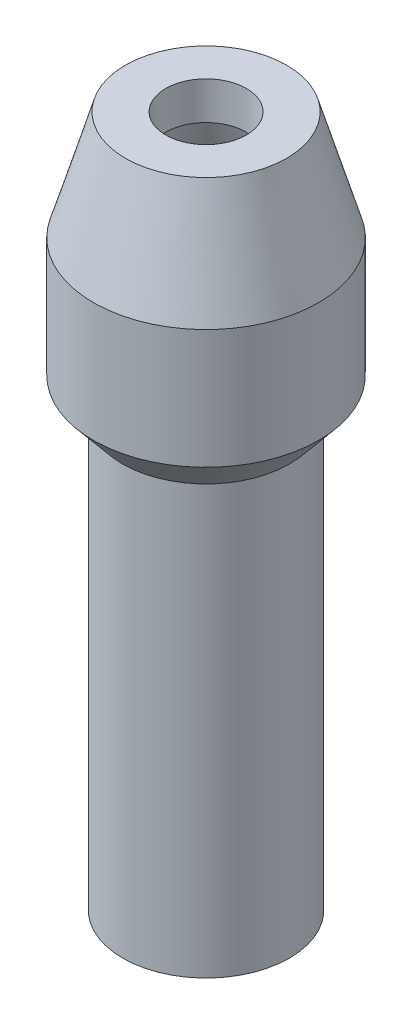
SolidWorks part; units mm, degrees
ref_plane "Front Plane" through (0, 0, 0) normal (0, 0, 1) x (1, 0, 0)
ref_plane "Top Plane" through (0, 0, 0) normal (0, 1, 0) x (1, 0, 0)
ref_plane "Right Plane" through (0, 0, 0) normal (1, 0, 0) x (0, 0, -1)
sketch "Sketch1" plane through (0, 0, 0) normal (0, 0, 1) x (1, 0, 0)
  line L0 (1.3508, 8.1834) -> (2.4158, 8.1834)
  line L1 (2.4158, 8.1834) -> (3.2608, 5.3049)
  line L2 (3.2608, 5.3049) -> (3.2608, 2.1549)
  line L3 (3.2608, 2.1549) -> (2.4858, 1.2256)
  line L4 (2.4858, 1.2256) -> (2.4858, -10.0744)
  line L5 (2.4858, -10.0744) -> (0.2858, -10.0744) construction
  line L6 (0.2858, -10.0744) -> (0.2858, 8.1834) construction
  line L7 (1.3508, 7.1834) -> (1.6672, 7.1834)
  line L8 (1.6672, 7.1834) -> (2.2608, 5.1611)
  line L9 (2.2608, 5.1611) -> (2.2608, 2.5171)
  line L10 (2.2608, 2.5171) -> (1.4858, 1.5879)
  line L11 (1.4858, 1.5879) -> (1.4858, -10.0744)
  line L12 (1.4858, -10.0744) -> (2.4858, -10.0744)
  line L13 (1.3508, 8.1834) -> (1.3508, 7.1834)
  line L14 (0.2858, 8.1834) -> (2.4158, 8.1834) construction
  line L15 (0.2858, 7.1834) -> (1.6672, 7.1834) construction
  dimension "D1" = 2.2
  dimension "D2" = 2.13
  dimension "D3" = 2.975
  dimension "D4" = 3.15
  dimension "D5" = 3
  dimension "D6" = 1.21
  dimension "D7" = 11.3
  dimension "D8" = 1
revolve "Revolve1" add sketch "Sketch1" angle 360 about L6
